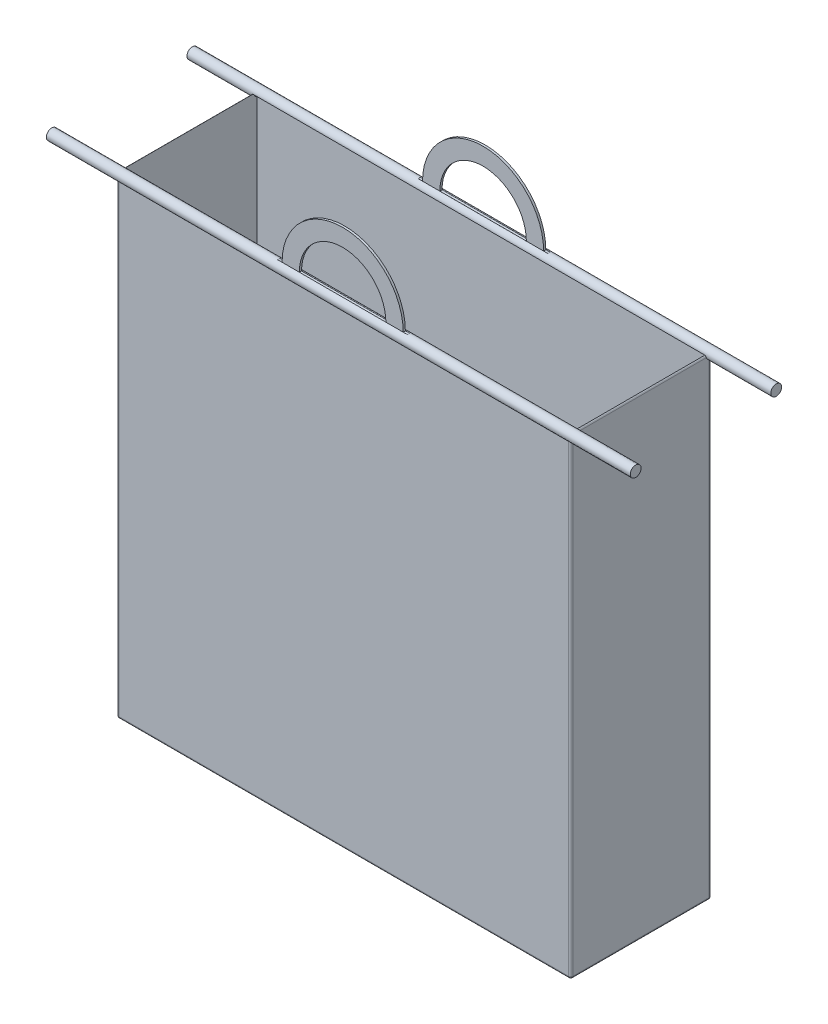
SolidWorks part; units mm, degrees
ref_plane "Alzado" through (0, 0, 0) normal (0, 0, 1) x (1, 0, 0)
ref_plane "Planta" through (0, 0, 0) normal (0, 1, 0) x (1, 0, 0)
ref_plane "Vista lateral" through (0, 0, 0) normal (1, 0, 0) x (0, 0, -1)
sketch "Croquis3" plane through (0, 0, 0) normal (1, 0, 0) x (0, 0, -1)
  circle A0 centre (0, 0) radius 6.35
  circle A1 centre (165.1, 0) radius 6.35
  dimension "D1" = 12.7
  dimension "D2" = 12.7
  dimension "D3" = 165.1
extrude "Saliente-Extruir3" add sketch "Croquis3" along normal blind 342.9 and the other way blind 342.9
sketch "Croquis4" plane through (0, 0, 0) normal (0, 1, 0) x (1, 0, 0)
  line L1 (-266.7, 165.1) -> (266.7, 165.1)
  line L2 (-266.7, 165.1) -> (-266.7, 0)
  line L3 (-266.7, 0) -> (266.7, 0)
  line L4 (266.7, 165.1) -> (266.7, 0)
  line L5 (-266.7, 165.1) -> (266.7, 0) construction
  line L6 (-266.7, 0) -> (266.7, 165.1) construction
  point P0 (0, 82.55)
  dimension "D1" = 533.4
  dimension "D2" = 165.1
extrude "Saliente-Extruir4" add sketch "Croquis4" against normal blind 555.498
shell "Vaciado3" thickness 1.27 removed face at (0, 0, -82.55)
fillet "Redondeo5" radius 2.54 10 edges at (266.7, 0, -82.55) (-266.7, 0, -82.55) (-266.7, -280.924, 0) (-266.7, -555.498, -82.55) (-266.7, -280.924, -165.1) (266.7, -280.924, 0) (0, -555.498, 0) (266.7, -555.498, -82.55) (0, -555.498, -165.1) (266.7, -280.924, -165.1)
sketch "Croquis5" plane through (0, 0, 0) normal (0, 1, 0) x (1, 0, 0)
  line L1 (-76.2, 166.2443) -> (76.2, 166.2443)
  line L2 (-76.2, 166.2443) -> (-76.2, 163.7043)
  line L3 (-76.2, 163.7043) -> (76.2, 163.7043)
  line L4 (76.2, 166.2443) -> (76.2, 163.7043)
  line L5 (-76.2, 166.2443) -> (76.2, 163.7043) construction
  line L6 (-76.2, 163.7043) -> (76.2, 166.2443) construction
  line L7 (-76.2, 1.27) -> (76.2, 1.27)
  line L8 (-76.2, 1.27) -> (-76.2, -1.27)
  line L9 (-76.2, -1.27) -> (76.2, -1.27)
  line L10 (76.2, 1.27) -> (76.2, -1.27)
  line L11 (-76.2, 1.27) -> (76.2, -1.27) construction
  line L12 (-76.2, -1.27) -> (76.2, 1.27) construction
  point P0 (0, 164.9743)
  point P5 (0, 0)
  dimension "D1" = 152.4
  dimension "D2" = 2.54
  dimension "D3" = 164.9743
  dimension "D4" = 152.4
  dimension "D5" = 2.54
extrude "Saliente-Extruir5" add sketch "Croquis5" along normal blind 101.6
sketch "Croquis6" plane through (0, 0, 1.27) normal (0, 0, 1) x (1, 0, 0)
  line L0 (76.2, 6.2217) -> (-76.2, 6.2217) construction
  line L1 (-76.2, 6.2217) -> (-50.8, 6.2217) construction
  line L2 (50.8, 6.2217) -> (76.2, 6.2217) construction
  line L3 (-76.2, 6.2217) -> (-76.2, 101.6) construction
  line L4 (-76.2, 101.6) -> (76.2, 101.6) construction
  line L5 (76.2, 101.6) -> (76.2, 6.2217) construction
  line L6 (-50.8, 6.2217) -> (50.8, 6.2217)
  arc A0 (76.2, 6.2217) -> (-76.2, 6.2217) centre (0, 6.2217) ccw construction
  arc A1 (50.8, 6.2217) -> (-50.8, 6.2217) centre (0, 6.2217) ccw
  dimension "D1" = 25.4
extrude "Cortar-Extruir2" cut sketch "Croquis6" against normal through all
sketch "Croquis7" plane through (0, 0, 1.27) normal (0, 0, 1) x (1, 0, 0)
  line L7 (-50.8, 6.2217) -> (50.8, 6.2217) construction
  line L8 (-71.12, 6.2217) -> (-76.2, 6.2217)
  line L9 (-76.2, 6.2217) -> (-76.2, 101.6)
  line L10 (-76.2, 101.6) -> (76.2, 101.6)
  line L11 (76.2, 101.6) -> (76.2, 6.2217)
  line L12 (76.2, 6.2217) -> (71.12, 6.2217)
  arc A1 (71.12, 6.2217) -> (-71.12, 6.2217) centre (0, 6.2217) ccw
  dimension "D1" = 71.12
extrude "Cortar-Extruir8" cut sketch "Croquis7" against normal through all
